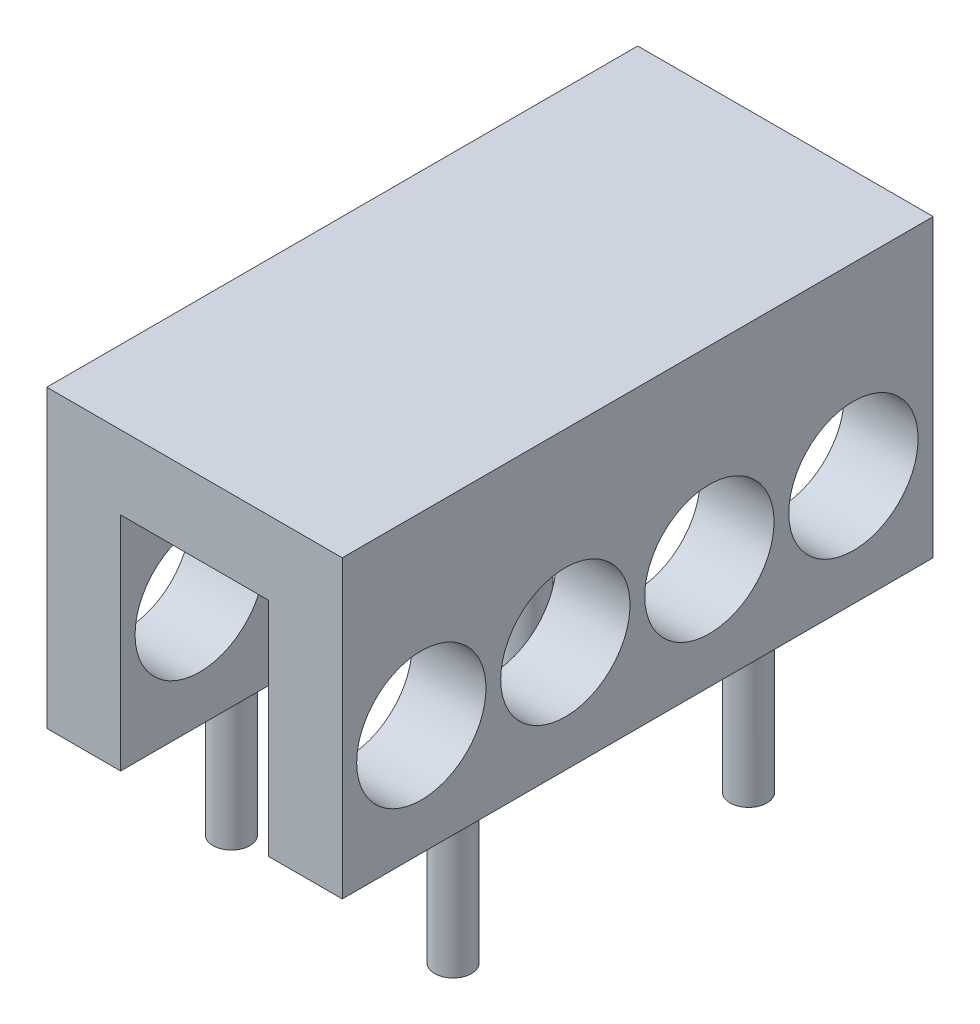
SolidWorks part; units mm, degrees
ref_plane "Front Plane" through (0, 0, 0) normal (0, 0, 1) x (1, 0, 0)
ref_plane "Top Plane" through (0, 0, 0) normal (0, 1, 0) x (1, 0, 0)
ref_plane "Right Plane" through (0, 0, 0) normal (1, 0, 0) x (0, 0, -1)
sketch "Sketch4" plane through (0, 0, 0) normal (0, 0, 1) x (1, 0, 0)
  line L0 (0, 0) -> (0, 50.8)
  line L1 (0, 50.8) -> (50.8, 50.8)
  line L2 (50.8, 50.8) -> (50.8, 0)
  line L3 (50.8, 0) -> (38.1, 0)
  line L4 (38.1, 0) -> (38.1, 38.136)
  line L5 (38.1, 38.136) -> (12.7, 38.136)
  line L6 (12.7, 38.136) -> (12.7, 0)
  line L7 (12.7, 0) -> (0, 0)
  dimension "D1" = 50.8
  dimension "D2" = 50.8
  dimension "D3" = 25.4
  dimension "D4" = 12.7
extrude "Boss-Extrude1" add sketch "Sketch4" along normal blind 101.6
sketch "Sketch5" plane through (0, 0, 0) normal (-1, 0, 0) x (0, 0, 1)
  line L0 (0, 50.8) -> (0, 0) construction
  line L1 (101.6, 0) -> (0, 0) construction
  circle A0 centre (13.716, 19.05) radius 11.1125
  circle A1 centre (38.481, 19.05) radius 11.1125
  circle A2 centre (63.246, 19.05) radius 11.1125
  circle A3 centre (88.011, 19.05) radius 11.1125
  dimension "D1" = 22.225
  dimension "D2" = 13.716
  dimension "D3" = 24.765
  dimension "D4" = 24.765
  dimension "D5" = 24.765
  dimension "D6" = 19.05
extrude "Cut-Extrude1" cut sketch "Sketch5" against normal through all
sketch "Sketch6" plane through (0, 0, 0) normal (0, -1, 0) x (1, 0, 0)
  line L0 (0, 101.6) -> (0, 0) construction
  line L1 (50.8, 101.6) -> (50.8, 0) construction
  line L2 (0, 0) -> (12.7, 0) construction
  line L3 (38.1, 0) -> (50.8, 0) construction
  circle A0 centre (6.35, 25.4) radius 3.175
  circle A1 centre (6.35, 76.2) radius 3.175
  circle A2 centre (44.45, 76.2) radius 3.175
  circle A3 centre (44.45, 25.4) radius 3.175
  dimension "D1" = 6.35
  dimension "D2" = 6.35
  dimension "D3" = 6.35
  dimension "D4" = 6.35
  dimension "D5" = 6.35
  dimension "D6" = 6.35
  dimension "D7" = 6.35
  dimension "D8" = 6.35
  dimension "D9" = 50.8
  dimension "D10" = 25.4
  dimension "D11" = 50.8
  dimension "D12" = 25.4
extrude "Boss-Extrude3" add sketch "Sketch6" along normal blind 25.4
